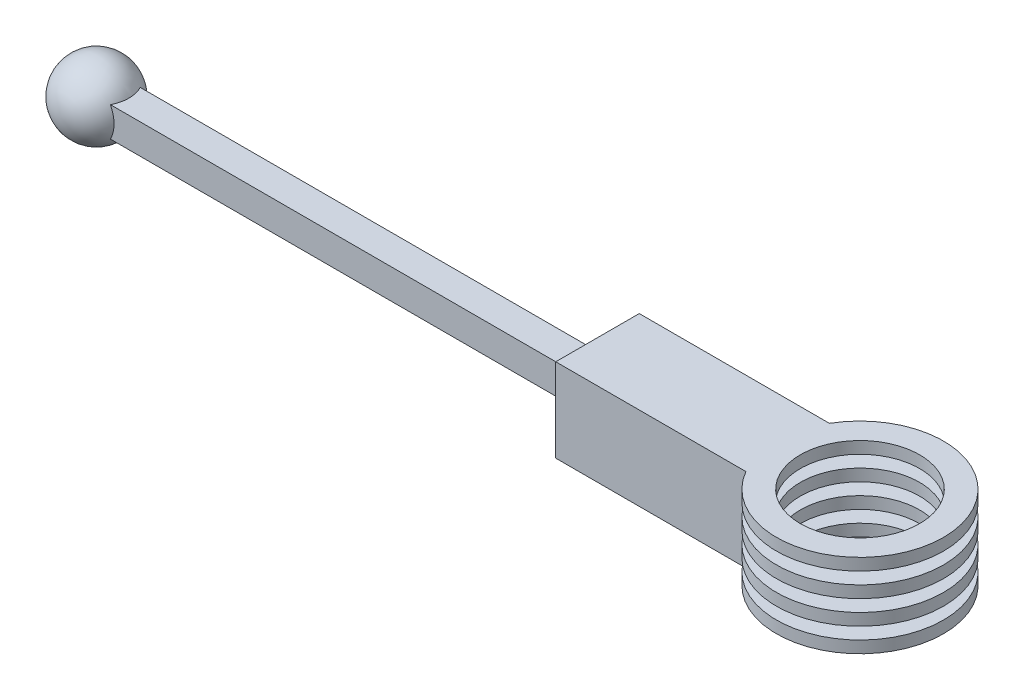
SolidWorks part; units mm, degrees
material "Galvanized Steel"
ref_plane "Front Plane" through (0, 0, 0) normal (0, 0, 1) x (1, 0, 0)
ref_plane "Top Plane" through (0, 0, 0) normal (0, 1, 0) x (1, 0, 0)
ref_plane "Right Plane" through (0, 0, 0) normal (1, 0, 0) x (0, 0, -1)
sketch "Sketch3" plane through (0, 0, 0) normal (0, 1, 0) x (1, 0, 0)
  line L0 (-508, 0) -> (-508, 304.8)
  arc A0 (-508, 0) -> (-508, 304.8) centre (-508, 152.4) ccw
  dimension "D3" = 592.4247
  dimension "D1" = 304.8
  dimension "D2" = 508
revolve "Revolve1" add sketch "Sketch3" angle 360 about L0
sketch "Sketch5" plane through (0, 0, 0) normal (1, 0, 0) x (0, 0, -1)
  line L0 (88.9, 63.5) -> (88.9, -63.5)
  line L1 (88.9, -63.5) -> (215.9, -63.5)
  line L2 (215.9, -63.5) -> (215.9, 63.5)
  line L3 (215.9, 63.5) -> (88.9, 63.5)
  point P2 (152.4, -63.5)
  dimension "D1" = 127
  dimension "D2" = 127
  dimension "D3" = 63.5
  dimension "D4" = 152.4
extrude "Boss-Extrude1" add sketch "Sketch5" along normal blind 1625.6 and the other way up to surface
sketch "Sketch6" plane through (1625.6, 0, 0) normal (1, 0, 0) x (0, 0, -1)
  line L0 (-25.4, 177.8) -> (-25.4, -177.8)
  line L1 (-25.4, -177.8) -> (330.2, -177.8)
  line L2 (330.2, -177.8) -> (330.2, 177.8)
  line L3 (330.2, 177.8) -> (-25.4, 177.8)
  line L4 (215.9, 63.5) -> (88.9, 63.5) construction
  line L5 (215.9, -63.5) -> (215.9, 63.5) construction
  circle A0 centre (152.4, 0) radius 152.4 construction
  point P2 (152.4, 177.8)
  point P7 (152.4, 63.5)
  point P8 (330.2, 0)
  point P11 (215.9, 0)
  dimension "D1" = 355.6
  dimension "D2" = 355.6
  dimension "D3" = 0
  dimension "D4" = 0
  dimension "D5" = 177.8
extrude "Boss-Extrude2" add sketch "Sketch6" along normal blind 762
sketch "Sketch7" plane through (0, 177.8, 0) normal (0, 1, 0) x (1, 0, 0)
  line L0 (2387.6, 330.2) -> (2387.6, -25.4) construction
  circle A0 centre (2743.2, 152.4) radius 355.6
  point P4 (2387.6, 152.4)
  dimension "D1" = 711.2
  dimension "D2" = 355.6
  dimension "D3" = 177.8
extrude "Boss-Extrude3" add sketch "Sketch7" against normal blind 355.6 separate body
sketch "Sketch8" plane through (2387.6, 0, 0) normal (1, 0, 0) x (0, 0, -1)
  line L4 (330.2, 177.8) -> (-25.4, 177.8)
  line L5 (-25.4, 177.8) -> (-25.4, -177.8)
  line L6 (-25.4, -177.8) -> (330.2, -177.8)
  line L7 (330.2, -177.8) -> (330.2, 177.8)
  line L8 (330.2, 177.8) -> (-25.4, 177.8)
  line L9 (-25.4, 177.8) -> (-25.4, -177.8)
  line L10 (-25.4, -177.8) -> (330.2, -177.8)
  line L11 (330.2, -177.8) -> (330.2, 177.8)
  dimension "D1" = 0
extrude "Boss-Extrude4" add sketch "Sketch8" along normal up to surface (47.6414 mm away) up to face at (2743.2, -177.8, 203.2)
sketch "Sketch9" plane through (0, 177.8, 0) normal (0, 1, 0) x (1, 0, 0)
  circle A0 centre (2743.2, 152.4) radius 254
  dimension "D1" = 508
extrude "Cut-Extrude1" cut sketch "Sketch9" against normal blind 355.6
ref_plane "Plane3" through (0, 0, -152.4) normal (0, 0, 1) x (1, 0, 0)
ref_plane "Plane2" through (1143, 0, 0) normal (1, 0, 0) x (0, 0, -1)
sketch "Sketch11" plane through (0, 0, -152.4) normal (0, 0, 1) x (1, 0, 0)
  line L0 (2743.2, 177.8) -> (2743.2, -177.8)
  line L3 (2997.2, 177.8) -> (2489.2, 177.8) construction
  line L4 (2435.2414, -177.8) -> (3098.8, -177.8) construction
  line L5 (2743.2, -177.8) -> (3098.8, -177.8)
  line L6 (3098.8, -177.8) -> (3098.8, 177.8)
  line L7 (3098.8, 177.8) -> (2743.2, 177.8)
  line L8 (2743.2, -127) -> (3098.8, -127)
  line L9 (2743.2, -76.2) -> (3098.8, -76.2)
  line L10 (2743.2, -25.4) -> (3098.8, -25.4)
  line L11 (2743.2, 25.4) -> (3098.8, 25.4)
  line L12 (2743.2, 76.2) -> (3098.8, 76.2)
  line L13 (2743.2, 127) -> (3098.8, 127)
  dimension "D1" = 50.8
  dimension "D2" = 50.8
  dimension "D3" = 50.8
  dimension "D4" = 50.8
  dimension "D5" = 50.8
  dimension "D6" = 50.8
revolve "Cut-Revolve1" cut sketch "Sketch11" angle 360 about L0 region at (2921, 101.6, -152.4) region at (2921, 0, -152.4) region at (2921, -101.6, -152.4)
split "Split1" bodies to split 108 resulting bodies 109 110 split by face at (1625.6, 0, -152.4)
